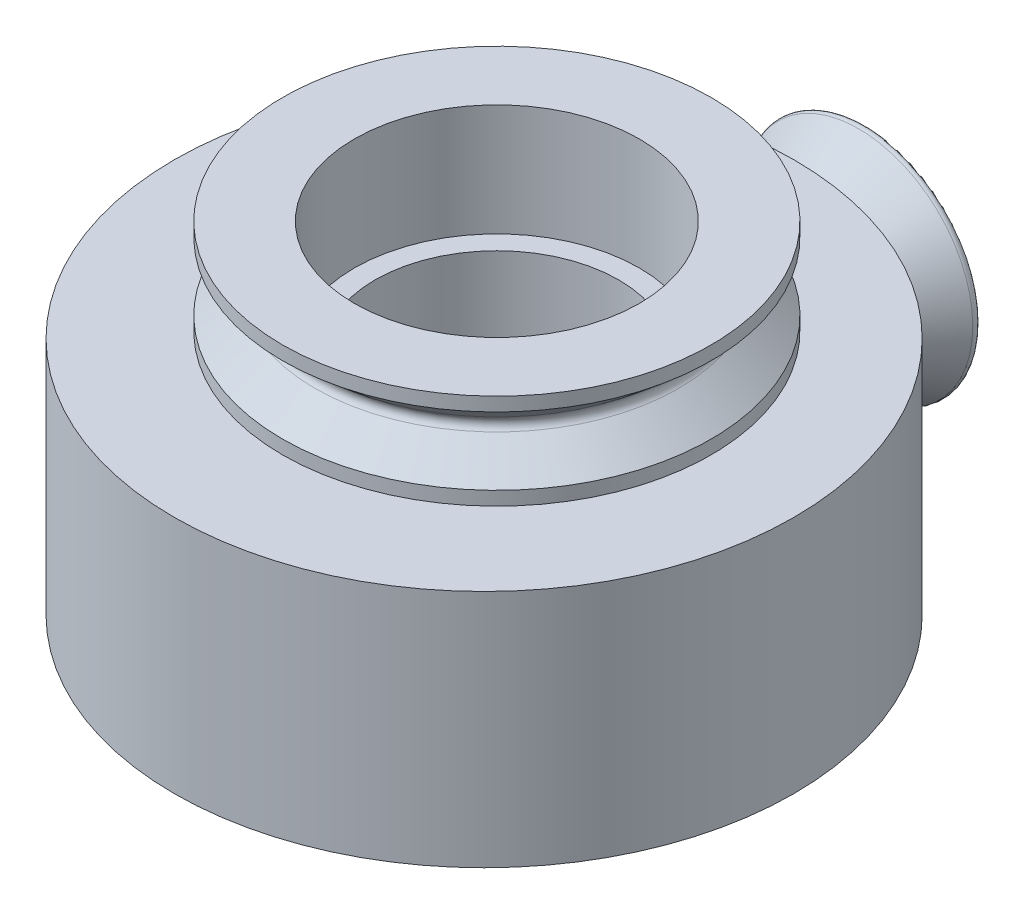
SolidWorks part; units mm, degrees
ref_plane "Front Plane" through (0, 0, 0) normal (0, 0, 1) x (1, 0, 0)
ref_plane "Top Plane" through (0, 0, 0) normal (0, 1, 0) x (1, 0, 0)
ref_plane "Right Plane" through (0, 0, 0) normal (1, 0, 0) x (0, 0, -1)
sketch "Sketch1" plane through (0, 0, 0) normal (0, 1, 0) x (1, 0, 0)
  circle A0 centre (0, 0) radius 20.65
  circle A1 centre (0, 0) radius 12.75
  dimension "D1" = 41.3
  dimension "D2" = 25.5
extrude "Boss-Extrude1" add sketch "Sketch1" along normal mid plane 15.95
sketch "Sketch2" plane through (0, 0, 0) normal (0, 1, 0) x (1, 0, 0)
  line L0 (-7.35, 25.45) -> (7.35, 25.45)
  line L1 (-4.285, 20.2005) -> (4.285, 20.2005)
  line L2 (-4.285, 20.2005) -> (-7.5966, 24.9791)
  line L3 (4.285, 20.2005) -> (7.5966, 24.9791) construction
  line L4 (0, 25.45) -> (0, 20.2005)
  line L5 (0, 0) -> (0, -7.3566) construction
  circle A0 centre (0, 0) radius 20.65 construction
  arc A1 (-7.35, 25.45) -> (-7.5966, 24.9791) centre (-7.35, 25.15) ccw
  arc A2 (7.35, 25.45) -> (7.5966, 24.9791) centre (7.35, 25.15) cw
  point P2 (0, 20.65)
  point P3 (0, 25.45)
  point P13 (7.65, 25.15)
  point P14 (-7.65, 25.15)
  dimension "D3" = 15.3
  dimension "D4" = 0.3
  dimension "D1" = 4.8
  dimension "D2" = 8.57
ref_axis "Axis1" through (0, 0, 23) along (0, 0, -1)
revolve "Revolve1" add sketch "Sketch2" angle 360 about axis through (0, 0, 23) along (0, 0, -1) region at (-3.1318, 0, -23.0808)
sketch "Sketch3" plane through (0, 0, -25.45) normal (0, 0, -1) x (-1, 0, 0)
  line L1 (0, 2.6558) -> (-2.3, 1.3279)
  line L2 (-2.3, 1.3279) -> (-2.3, -1.3279)
  line L3 (-2.3, -1.3279) -> (0, -2.6558)
  line L4 (0, -2.6558) -> (2.3, -1.3279)
  line L5 (2.3, -1.3279) -> (2.3, 1.3279)
  line L6 (2.3, 1.3279) -> (0, 2.6558)
  circle A0 centre (0, 0) radius 2.3 construction
  dimension "D1" = 4.6
extrude "Cut-Extrude1" cut sketch "Sketch3" against normal blind 4.6
sketch "Sketch4" plane through (0, 0, 0) normal (0, 1, 0) x (1, 0, 0)
  line L0 (-3.5, 12.95) -> (3.5, 12.95)
  line L1 (7.35, 25.45) -> (-7.35, 25.45) construction
  line L2 (-3.5, 12.95) -> (-4.45, 11.9482)
  line L3 (-4.45, 11.9482) -> (4.45, 11.9482)
  line L4 (4.45, 11.9482) -> (3.5, 12.95)
  line L5 (0, 12.95) -> (0, 11.9482)
  circle A0 centre (0, 0) radius 12.75 construction
  dimension "D1" = 12.5
  dimension "D2" = 8.9
  dimension "D3" = 7
revolve "Cut-Revolve2" cut sketch "Sketch4" angle 360 about axis through (0, 0, 23) along (0, 0, -1) region at (-1.997, 0, -12.4292)
sketch "Sketch5" plane through (0, 0, 0) normal (0, 1, 0) x (1, 0, 0)
  line L0 (0, -23) -> (0, 28.7) construction
  circle A0 centre (0, 0) radius 12.55
  circle A1 centre (0, 0.8509) radius 8.125
  circle A2 centre (0, 0) radius 12.75 construction
  dimension "D1" = 0.2
  dimension "D2" = 16.25
  dimension "D3" = 0.8509
extrude "Boss-Extrude2" add sketch "Sketch5" along normal up to surface and the other way up to surface separate body up to face at (0, 7.975, 20.65) other way up to face at (0, -7.975, 20.65)
sketch "Sketch6" plane through (0, 7.975, 0) normal (0, 1, 0) x (1, 0, 0)
  circle A0 centre (0, 0.8509) radius 9.5
  circle A1 centre (0, 0.8509) radius 8.125 construction
  dimension "D1" = 19
extrude "Cut-Extrude2" cut sketch "Sketch6" against normal blind 1.1
mirror "Mirror1" about plane through (0, 0, 0) normal (0, 1, 0) of "Cut-Extrude2"
sketch "Sketch7" plane through (0, 7.975, 0) normal (0, 1, 0) x (1, 0, 0)
  circle A0 centre (0, 0.8509) radius 14.2875
  circle A1 centre (0, 0.8509) radius 9.5
  circle A2 centre (0, 0.8509) radius 8.125 construction
  circle A3 centre (0, 0.8509) radius 9.5 construction
  dimension "D1" = 28.575
extrude "Boss-Extrude4" add sketch "Sketch7" along normal blind 6.35
ref_axis "Axis2" through (0, 38.6511, -0.8509) along (0, -1, 0)
sketch "Sketch8" plane through (0, 0, 0) normal (1, 0, 0) x (0, 0, -1)
  line L0 (15.1384, 13.4113) -> (12.9588, 11.5824)
  line L1 (15.1384, 7.975) -> (15.1384, 14.325) construction
  line L2 (12.9588, 10.7176) -> (15.1384, 8.8887)
  line L3 (15.1384, 7.975) -> (15.1384, 14.325) construction
  line L4 (15.1384, 8.8887) -> (15.1384, 13.4113)
  line L5 (15.1384, 14.325) -> (15.1384, 13.4113) construction
  line L6 (15.1384, 8.8887) -> (15.1384, 7.975) construction
  line L7 (20.65, 7.975) -> (-20.65, 7.975) construction
  line L8 (15.1384, 7.975) -> (15.1384, 14.325) construction
  line L9 (15.1384, 11.15) -> (12.7572, 11.15) construction
  arc A0 (12.9588, 11.5824) -> (12.9588, 10.7176) centre (13.3216, 11.15) ccw
  dimension "D1" = 0.5644
  dimension "D2" = 40
  dimension "D3" = 2.3813
revolve "Cut-Revolve3" cut sketch "Sketch8" angle 360 about axis through (0, 38.6511, -0.8509) along (0, -1, 0)
sketch "Sketch9" plane through (0, 0, -25.45) normal (0, 0, -1) x (-1, 0, 0)
  circle A0 centre (0, 0) radius 3
  dimension "D1" = 6
extrude "Cut-Extrude3" cut sketch "Sketch9" against normal blind 13.97
chamfer "Chamfer1" distance 1.016 angle 45 1 edges at (-3, 0, -11.48)
mirror "Mirror2" about plane through (0, 0, 0) normal (0, 0, 1) of "Chamfer1", "Cut-Extrude3"
